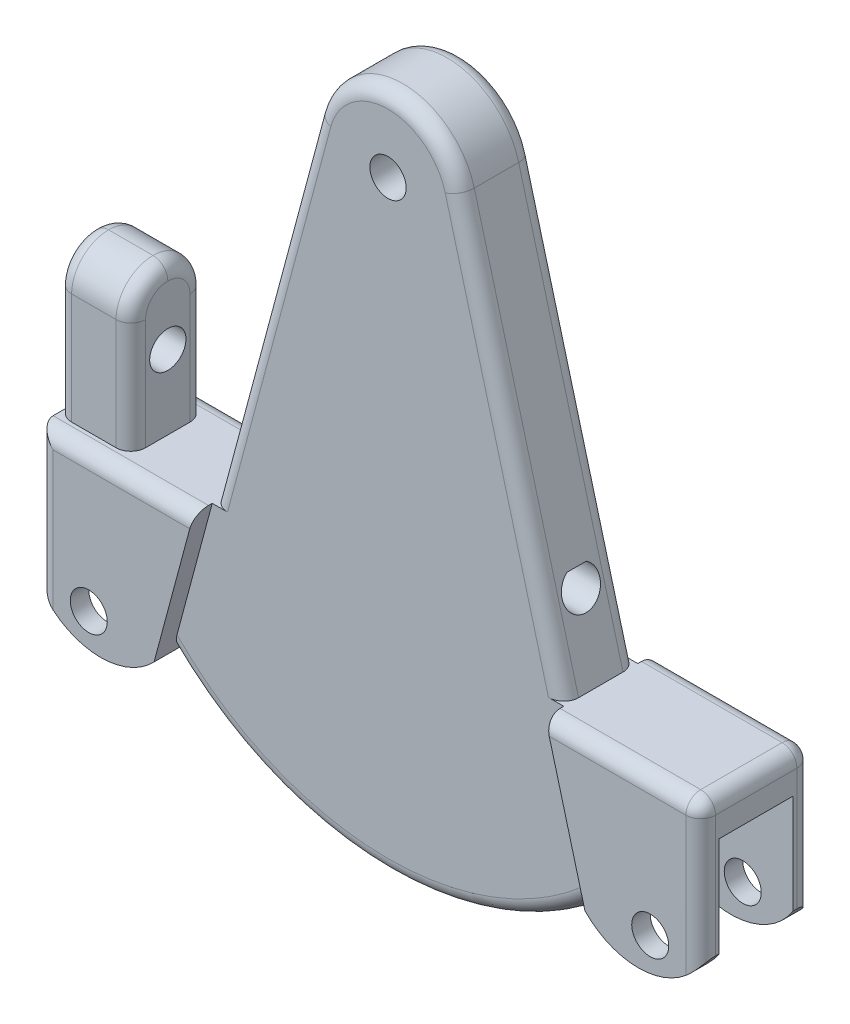
SolidWorks part; units mm, degrees
ref_plane "Front Plane" through (0, 0, 0) normal (0, 0, 1) x (1, 0, 0)
ref_plane "Top Plane" through (0, 0, 0) normal (0, 1, 0) x (1, 0, 0)
ref_plane "Right Plane" through (0, 0, 0) normal (1, 0, 0) x (0, 0, -1)
sketch "Sketch2" plane through (0, 0, 0) normal (0, 0, 1) x (1, 0, 0)
  line L0 (26.67, -25.4) -> (44.5655, 41.387)
  line L1 (0, 0) -> (12.7, 0)
  line L2 (0, 0) -> (0, -31.75)
  line L4 (12.7, 0) -> (12.7, -25.4)
  line L7 (12.7, -25.4) -> (26.67, -25.4)
  line L10 (69.1, 41.387) -> (86.9956, -25.4)
  line L13 (56.8328, 38.1) -> (56.8328, -25.4) construction
  line L14 (26.67, -25.4) -> (86.9956, -25.4) construction
  line L15 (0, -31.75) -> (19.8641, -50.8)
  line L16 (26.67, -25.4) -> (19.8641, -50.8) construction
  line L17 (86.9956, -25.4) -> (93.8015, -50.8) construction
  line L18 (93.8015, -50.8) -> (113.6656, -31.75)
  line L19 (113.6656, -31.75) -> (113.6656, -25.4)
  line L20 (113.6656, -25.4) -> (86.9956, -25.4)
  arc A0 (44.5655, 41.387) -> (69.1, 41.387) centre (56.8328, 38.1) cw
  arc A1 (19.8641, -50.8) -> (93.8015, -50.8) centre (56.8328, -12.2515) ccw
  circle A2 centre (56.8328, 38.1) radius 3.1115
  dimension "D8" = 6.223
  dimension "D9" = 12.7
  dimension "D1" = 15
  dimension "D2" = 15
  dimension "D3" = 25.4
  dimension "D4" = 12.7
  dimension "D5" = 6.35
  dimension "D6" = 13.97
  dimension "D7" = 19.05
  dimension "D10" = 63.5
  dimension "D11" = 19.05
  dimension "D12" = 26.67
extrude "Boss-Extrude1" add sketch "Sketch2" along normal mid plane 12.7
sketch "Sketch3" plane through (0, 0, 0) normal (-1, 0, 0) x (0, 0, 1)
  line L1 (0, 0) -> (0, -25.4) construction
  line L2 (6.35, 0) -> (-6.35, 0) construction
  line L4 (6.35, -25.4) -> (6.35, 0) construction
  circle A0 centre (0, -12.7) radius 3.1115
  dimension "D1" = 6.223
extrude "Cut-Extrude1" cut sketch "Sketch3" against normal blind 12.7
sketch "Sketch5" plane through (12.7, 0, 0) normal (1, 0, 0) x (0, 0, -1)
  line L0 (1.651, -9.9139) -> (-1.651, -9.9139)
  arc A0 (-1.651, -9.9139) -> (1.651, -9.9139) centre (0, -12.7) ccw
  circle A1 centre (0, -12.7) radius 3.1115 construction
  dimension "D1" = 6.477
  dimension "D2" = 3.302
extrude "Cut-Extrude3" cut sketch "Sketch5" along normal through all
sketch "Sketch9" plane through (0, 0, 6.35) normal (0, 0, 1) x (1, 0, 0)
  line L0 (26.67, -25.4) -> (19.8641, -50.8)
  line L1 (44.5655, 41.387) -> (26.67, -25.4) construction
  line L2 (0, -25.4) -> (0, -48.8538)
  line L3 (0, -31.75) -> (19.8641, -50.8) construction
  line L4 (0, -25.4) -> (26.67, -25.4)
  line L5 (56.8328, 38.1) -> (56.8328, -65.6619) construction
  line L6 (113.6656, -25.4) -> (86.9956, -25.4)
  line L7 (113.6656, -25.4) -> (113.6656, -48.8538)
  line L8 (86.9956, -25.4) -> (93.8015, -50.8)
  circle A0 centre (8.6605, -48.8538) radius 3.175
  arc A1 (0, -48.8538) -> (19.8641, -50.8) centre (10.698, -42.0095) ccw
  arc A2 (19.8641, -50.8) -> (93.8015, -50.8) centre (56.8328, -12.2515) ccw construction
  arc A3 (113.6656, -48.8538) -> (93.8015, -50.8) centre (102.9676, -42.0095) cw
  circle A4 centre (105.005, -48.8538) radius 3.175
  dimension "D1" = 6.35
  dimension "D3" = 12.7
  dimension "D2" = 6.35
extrude "Boss-Extrude2" add sketch "Sketch9" along normal blind 3.175
mirror "Mirror4" about plane through (0, 0, 0) normal (0, 0, 1) of "Boss-Extrude2"
fillet "Fillet1" radius 6.35 2 edges at (6.35, 0, -6.35) (6.35, 0, 6.35)
fillet "Fillet2" radius 2.54 26 edges at (12.7, -15.875, -6.35) (12.7, -15.875, 6.35) (12.7, -1.8599, 4.4901) (0, -15.875, 6.35) (0, -1.8599, 4.4901) (0, -1.8599, -4.4901) (78.0478, 7.9935, -6.35) (56.8328, 50.8, -6.35) (78.0478, 7.9935, 6.35) (56.8328, 50.8, 6.35) (113.6656, -37.1269, 9.525) (113.6656, -37.1269, -9.525) (0, -31.75, 0) (0, -37.1269, -9.525) (0, -37.1269, 9.525) (56.8328, -65.6619, -6.35) (56.8328, -65.6619, 6.35) (100.3306, -25.4, -9.525) (113.6656, -25.4, 0) (100.3306, -25.4, 9.525) (12.7, -1.8599, -4.4901) (0, -15.875, -6.35) (13.335, -25.4, -9.525) (13.335, -25.4, 9.525) (35.6178, 7.9935, -6.35) (35.6178, 7.9935, 6.35)
